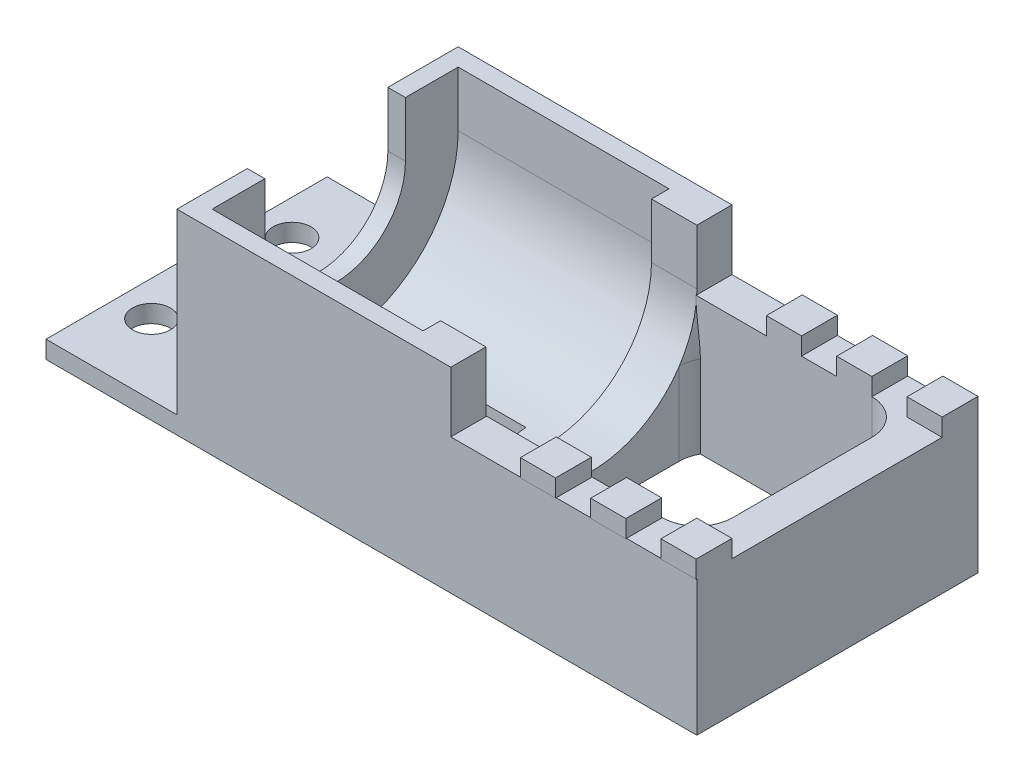
SolidWorks part; units mm, degrees
ref_plane "Front Plane" through (0, 0, 0) normal (0, 0, 1) x (1, 0, 0)
ref_plane "Top Plane" through (0, 0, 0) normal (0, 1, 0) x (1, 0, 0)
ref_plane "Right Plane" through (0, 0, 0) normal (1, 0, 0) x (0, 0, -1)
sketch "Sketch1" plane through (0, 0, 0) normal (0, 0, 1) x (1, 0, 0)
  line L1 (-76.2, -50.8) -> (76.2, -50.8)
  line L2 (-76.2, -50.8) -> (-76.2, 0)
  line L3 (-76.2, 0) -> (76.2, 0)
  line L4 (76.2, -50.8) -> (76.2, 0)
  line L5 (-76.2, -50.8) -> (76.2, 0) construction
  line L6 (-76.2, 0) -> (76.2, -50.8) construction
  point P0 (0, 0)
  dimension "D1" = 152.4
  dimension "D2" = 50.8
  dimension "D3" = 76.2
extrude "Boss-Extrude1" add sketch "Sketch1" along normal mid plane 50.8
sketch "Sketch2" plane through (0, 0, 0) normal (0, 0, 1) x (1, 0, 0)
  line L0 (-152.4829, -25.4) -> (19.6294, -25.4) construction
  line L1 (-49.3609, -3.175) -> (-49.3609, -12.7)
  line L2 (76.2, 0) -> (-76.2, 0) construction
  line L3 (76.2, 0) -> (-76.2, 0) construction
  line L4 (-11.2609, -3.175) -> (-11.2609, -6.35)
  line L5 (-11.2609, -25.4) -> (-11.2609, -3.175) construction
  line L6 (-128.4172, -25.4) -> (-157.8092, -25.4)
  line L7 (19.6294, -25.4) -> (20.7431, -25.4)
  line L8 (-607.3619, -25.4) -> (19.6294, -25.4) construction
  line L9 (-49.3609, -3.175) -> (-11.2609, -3.175)
  line L10 (19.6294, -25.4) -> (-128.4172, -25.4)
  line L11 (-11.2609, -6.35) -> (-4.6569, -6.35)
  line L12 (-4.6569, -6.35) -> (-4.6569, -15.494)
  line L13 (-4.6569, -15.494) -> (20.7431, -15.494)
  line L14 (-49.3609, -12.7) -> (-220.2024, -12.7)
  line L15 (-220.2024, -12.7) -> (-220.2024, -25.4)
  line L16 (-220.2024, -25.4) -> (-157.8092, -25.4)
  line L20 (20.7431, -15.494) -> (20.7431, -25.4)
  line L21 (-76.2, 0) -> (-76.2, -50.8) construction
  point P23 (-11.2609, -25.4)
  dimension "D1" = 22.225
  dimension "D2" = 38.1
  dimension "D3" = 25.4
  dimension "D4" = 32.004
  dimension "D5" = 9.906
  dimension "D6" = 3.175
  dimension "D7" = 26.8391
  dimension "D8" = 25.4
  dimension "D9" = 12.7
revolve "Cut-Revolve1" cut sketch "Sketch2" angle 360 about L0
sketch "Sketch38" plane through (20.7431, 0, 0) normal (1, 0, 0) x (0, 0, -1)
  line L1 (-10, -35.4) -> (10, -35.4)
  line L2 (-10, -35.4) -> (-10, -15.4)
  line L3 (-10, -15.4) -> (10, -15.4)
  line L4 (10, -35.4) -> (10, -15.4)
  line L5 (-10, -35.4) -> (10, -15.4) construction
  line L6 (-10, -15.4) -> (10, -35.4) construction
  circle A0 centre (0, -25.4) radius 9.906 construction
  point P1 (0, -25.4)
  dimension "D1" = 20
  dimension "D2" = 20
extrude "Cut-Extrude33" cut sketch "Sketch38" against normal offset from surface (23.8125 mm away) 1.5875 up to face at (-4.6569, -25.4, 19.05)
sketch "Sketch37" plane through (76.2, 0, 0) normal (1, 0, 0) x (0, 0, -1)
  line L0 (25.4, -50.8) -> (25.4, 0) construction
  line L1 (-25.4, 0) -> (25.4, 0)
  line L2 (-25.4, 0) -> (-25.4, -25.4)
  line L3 (-25.4, -25.4) -> (25.4, -25.4)
  line L4 (25.4, 0) -> (25.4, -25.4)
  line L5 (10, -35.4) -> (10, -15.4) construction
  point P7 (0, -25.4)
  point P11 (0, 0)
  point P14 (10, -25.4)
extrude "Cut-Extrude32" cut sketch "Sketch37" against normal through all
sketch "Sketch39" plane through (0, -25.4, 0) normal (0, 1, 0) x (1, 0, 0)
  line L24 (-49.3609, -12.7) -> (-76.2, -12.7)
  line L25 (-76.2, -12.7) -> (-76.2, -25.4)
  line L26 (-76.2, -25.4) -> (76.2, -25.4)
  line L27 (76.2, -25.4) -> (76.2, 25.4)
  line L28 (76.2, 25.4) -> (-76.2, 25.4)
  line L29 (-76.2, 25.4) -> (-76.2, 12.7)
  line L30 (-76.2, 12.7) -> (-49.3609, 12.7)
  line L31 (-49.3609, 12.7) -> (-49.3609, 22.225)
  line L32 (-49.3609, 22.225) -> (-11.2609, 22.225)
  line L33 (-11.2609, 22.225) -> (-11.2609, 19.05)
  line L34 (-11.2609, 19.05) -> (-4.6569, 19.05)
  line L35 (-4.6569, 19.05) -> (-4.6569, 9.906)
  line L36 (-4.6569, 9.906) -> (-3.0694, 9.906)
  line L37 (-3.0694, 9.906) -> (-3.0694, 10)
  line L38 (-3.0694, 9.906) -> (-3.0694, 10)
  line L39 (20.7431, 10) -> (20.7431, -10)
  line L40 (-3.0694, 10) -> (20.7431, 10)
  line L41 (-3.0694, 10) -> (20.7431, 10)
  line L42 (-3.0694, -9.906) -> (-4.6569, -9.906)
  line L43 (-4.6569, -9.906) -> (-4.6569, -19.05)
  line L44 (-4.6569, -19.05) -> (-11.2609, -19.05)
  line L45 (-11.2609, -19.05) -> (-11.2609, -22.225)
  line L46 (-11.2609, -22.225) -> (-49.3609, -22.225)
  line L47 (-49.3609, -22.225) -> (-49.3609, -12.7)
  line L48 (-49.3609, -12.7) -> (-76.2, -12.7)
  line L49 (-76.2, -12.7) -> (-76.2, -25.4)
  line L50 (-76.2, -25.4) -> (76.2, -25.4)
  line L51 (76.2, -25.4) -> (76.2, 25.4)
  line L52 (76.2, 25.4) -> (-76.2, 25.4)
  line L53 (-76.2, 25.4) -> (-76.2, 12.7)
  line L54 (-76.2, 12.7) -> (-49.3609, 12.7)
  line L55 (-49.3609, 12.7) -> (-49.3609, 22.225)
  line L56 (-49.3609, 22.225) -> (-11.2609, 22.225)
  line L57 (-11.2609, 22.225) -> (-11.2609, 19.05)
  line L58 (-11.2609, 19.05) -> (-4.6569, 19.05)
  line L59 (-4.6569, 19.05) -> (-4.6569, 9.906)
  line L60 (-4.6569, 9.906) -> (-3.0694, 9.906)
  line L61 (20.7431, -10) -> (-3.0694, -10)
  line L62 (20.7431, -10) -> (-3.0694, -10)
  line L63 (20.7431, 10) -> (20.7431, -10)
  line L64 (-3.0694, -10) -> (-3.0694, -9.906)
  line L65 (-3.0694, -10) -> (-3.0694, -9.906)
  line L66 (-3.0694, -9.906) -> (-4.6569, -9.906)
  line L67 (-4.6569, -9.906) -> (-4.6569, -19.05)
  line L68 (-4.6569, -19.05) -> (-11.2609, -19.05)
  line L69 (-11.2609, -19.05) -> (-11.2609, -22.225)
  line L70 (-11.2609, -22.225) -> (-49.3609, -22.225)
  line L71 (-49.3609, -22.225) -> (-49.3609, -12.7)
  dimension "D1" = 0
extrude "Boss-Extrude5" add sketch "Sketch39" along normal blind 25.4
ref_axis "Axis1" through (-3.0694, -25.4, 0) along (-1, 0, 0)
ref_plane "Plane_Mid" through (0, -25.4, 0) normal (0, 1, 0) x (1, 0, 0)
sketch "Sketch45" plane through (0, 0, 0) normal (0, 0, 1) x (1, 0, 0)
  line L2 (76.2, 0) -> (-3.0694, 0)
  line L4 (76.2, 0) -> (76.2, -19.05)
  line L5 (76.2, -19.05) -> (-3.0694, -19.05)
  line L6 (-3.0694, -25.4) -> (-4.6569, -25.4) construction
  line L8 (-3.0694, 0) -> (-3.0694, -19.05)
  dimension "D2" = 6.35
extrude "Cut-Extrude54" cut sketch "Sketch45" against normal through all both and the other way through all
sketch "Sketch53" plane through (20.7431, 0, 0) normal (-1, 0, 0) x (0, 0, 1)
  circle A0 centre (0, -25.4) radius 2
  dimension "D1" = 4
extrude "Cut-Extrude46" cut sketch "Sketch53" against normal blind 0.0254
sketch "Sketch72" plane through (0, -19.05, 0) normal (0, 1, 0) x (1, 0, 0)
  line L0 (-3.0694, -25.4) -> (-3.0694, -13.175)
  line L1 (-3.0694, -10) -> (-3.0694, -25.4) construction
  line L2 (-3.0694, -13.175) -> (23.9181, -13.175)
  line L3 (23.9181, -13.175) -> (23.9181, 13.175)
  line L4 (23.9181, 13.175) -> (-3.0694, 13.175)
  line L5 (-3.0694, 25.4) -> (-3.0694, 10) construction
  line L6 (-3.0694, 13.175) -> (-3.0694, 25.4)
  line L7 (-3.0694, 25.4) -> (76.2, 25.4)
  line L8 (76.2, 25.4) -> (76.2, -25.4)
  line L9 (76.2, -25.4) -> (-3.0694, -25.4)
  line L10 (-3.0694, -10) -> (20.7431, -10) construction
  line L11 (-3.0694, -10) -> (-3.0694, -13.175) construction
  line L12 (20.7431, -10) -> (23.9181, -10) construction
  line L13 (20.7431, 10) -> (20.7431, 13.175) construction
  dimension "D1" = 3.175
sketch "Sketch61" plane through (-4.6569, 0, 0) normal (-1, 0, 0) x (0, 0, 1)
  circle A0 centre (0, -25.4) radius 9.525
  circle A1 centre (0, -25.4) radius 9.906
  arc A2 (-9.906, -25.4) -> (9.906, -25.4) centre (0, -25.4) ccw construction
  dimension "D1" = 19.05
extrude "Boss-Extrude11" add sketch "Sketch61" against normal up to surface (1.5875 mm away) up to face at (-3.0694, -17.3088, 0)
sketch "Sketch70" plane through (0, 0, 0) normal (0, 1, 0) x (1, 0, 0)
  line L1 (-4.6569, 9.906) -> (-3.0694, 9.906)
  line L2 (-4.6569, 9.906) -> (-4.6569, -9.906)
  line L3 (-4.6569, -9.906) -> (-3.0694, -9.906)
  line L4 (-3.0694, 9.906) -> (-3.0694, -9.906)
extrude "Boss-Extrude17" add sketch "Sketch70" against normal up to next
sketch "Sketch76" plane through (0, -35.4, 0) normal (0, 1, 0) x (1, 0, 0)
  line L5 (-3.0694, -10) -> (20.7431, -10)
  line L6 (20.7431, -10) -> (20.7431, 10)
  line L9 (20.7431, 10) -> (-3.0694, 10)
  line L10 (-3.0694, 10) -> (-3.0694, -10)
  line L11 (-3.0694, -10) -> (20.7431, -10)
  line L12 (20.7431, -10) -> (20.7431, 10)
  line L13 (20.7431, 10) -> (-3.0694, 10)
  line L14 (-3.0694, 10) -> (-3.0694, -10)
  dimension "D1" = 0
extrude "Cut-Extrude58" cut sketch "Sketch76" against normal through all
sketch "Sketch86" plane through (0, -19.05, 0) normal (0, 1, 0) x (1, 0, 0)
  line L8 (-3.0694, -25.4) -> (76.2, -25.4)
  line L9 (-3.0694, -25.4) -> (76.2, -25.4)
  line L10 (76.2, -25.4) -> (76.2, 25.4)
  line L11 (76.2, -25.4) -> (76.2, 25.4)
  line L12 (76.2, 25.4) -> (-3.0694, 25.4)
  line L13 (76.2, 25.4) -> (-3.0694, 25.4)
  line L16 (20.7431, 10) -> (20.7431, -10)
  line L25 (20.7431, -10) -> (-3.0694, -10)
  line L26 (-3.0694, -10) -> (-3.0694, -25.4)
  line L30 (-3.0694, 25.4) -> (-3.0694, 10)
  line L31 (-3.0694, 10) -> (20.7431, 10)
  line L32 (20.7431, 10) -> (20.7431, -10)
  line L41 (20.7431, -10) -> (-3.0694, -10)
  line L42 (-3.0694, -10) -> (-3.0694, -25.4)
  line L46 (-3.0694, 25.4) -> (-3.0694, 10)
  line L47 (-3.0694, 10) -> (20.7431, 10)
  dimension "D1" = 0
extrude "Boss-Extrude24" add sketch "Sketch86" along normal blind 3.175
ref_plane "Plane1" through (-74.7609, 0, 0) normal (1, 0, 0) x (0, 0, -1)
sketch "Sketch89" plane through (0, 0, 0) normal (0, 1, 0) x (1, 0, 0)
  line L0 (-3.0694, 0) -> (-4.6569, 0) construction
  line L1 (-38.3605, -3.81) -> (-18.7213, -3.81)
  line L2 (-38.3605, -3.81) -> (-38.3605, 3.81)
  line L3 (-38.3605, 3.81) -> (-18.7213, 3.81)
  line L4 (-18.7213, -3.81) -> (-18.7213, 3.81)
  line L5 (-38.3605, -3.81) -> (-18.7213, 3.81) construction
  line L6 (-38.3605, 3.81) -> (-18.7213, -3.81) construction
  point P4 (-28.5409, 0)
extrude "Cut-Extrude64" cut sketch "Sketch89" against normal through all both and the other way through all
sketch "Sketch77" plane through (0, 0, 0) normal (0, 0, 1) x (1, 0, 0)
  line L0 (20.7431, -24.0284) -> (23.9181, -24.0284)
  line L1 (-3.0694, -26.7716) -> (20.7431, -26.7716)
  line L2 (-3.0694, -26.7716) -> (-3.0694, -24.0284)
  line L3 (-3.0694, -24.0284) -> (20.7431, -24.0284)
  line L4 (20.7431, -26.7716) -> (20.7431, -24.0284) construction
  line L5 (-3.0694, -26.7716) -> (20.7431, -24.0284) construction
  line L6 (-3.0694, -24.0284) -> (20.7431, -26.7716) construction
  line L7 (23.9181, -24.0284) -> (23.9181, -26.7716)
  line L8 (23.9181, -26.7716) -> (20.7431, -26.7716)
  line L9 (-3.0694, -25.4) -> (-4.6569, -25.4) construction
  line L10 (-3.0694, -15.875) -> (-3.0694, -50.8) construction
  line L11 (20.7431, -15.875) -> (20.7431, -50.8) construction
  point P0 (8.8368, -25.4)
  dimension "D1" = 3.175
  dimension "D2" = 2.7432
extrude "Cut-Extrude59" cut sketch "Sketch77" against normal through all both and the other way through all
sketch "Sketch96" plane through (0, 0, 25.4) normal (0, 0, 1) x (1, 0, 0)
  line L0 (-39.6347, 0) -> (-39.6347, -50.8) construction
  line L1 (-76.2, 0) -> (-3.0694, 0) construction
  line L2 (-76.2, -50.8) -> (76.2, -50.8) construction
  line L3 (-55.5097, -15.4427) -> (-23.7597, -15.4427)
  arc A0 (-23.7597, -15.4427) -> (-55.5097, -15.4427) centre (-39.6347, -32.1115) ccw
  point P8 (-39.6347, -15.4427)
  point P10 (-39.6347, -9.0927)
  dimension "D2" = 6.35
  dimension "D1" = 31.75
extrude "Cut-Extrude71" cut sketch "Sketch96" against normal through all
sketch "Sketch97" plane through (0, 0, 0) normal (0, 1, 0) x (1, 0, 0)
  line L0 (-76.2, -25.4) -> (-3.0694, -25.4) construction
  line L1 (-76.2, 25.4) -> (-52.5359, 25.4)
  line L2 (-76.2, 25.4) -> (-76.2, -25.4)
  line L3 (-76.2, -25.4) -> (-52.5359, -25.4)
  line L4 (-52.5359, 25.4) -> (-52.5359, -25.4)
  line L5 (-49.3609, 12.7) -> (-49.3609, 22.225) construction
  dimension "D1" = 3.175
extrude "Cut-Extrude72" cut sketch "Sketch97" against normal offset from surface (47.625 mm away) 3.175 up to face at (-28.5409, -50.8, 0)
sketch "Sketch98" plane through (0, -47.625, 0) normal (0, 1, 0) x (1, 0, 0)
  line L0 (-76.2, -25.4) -> (-76.2, 25.4) construction
  circle A0 centre (-69.85, 12.7) radius 3.429
  circle A1 centre (-57.15, 12.7) radius 3.429
  circle A2 centre (-57.15, 0) radius 3.429
  circle A3 centre (-57.15, -12.7) radius 3.429
  circle A4 centre (-69.85, 0) radius 3.429
  circle A5 centre (-69.85, -12.7) radius 3.429
  dimension "D1" = 6.858
  dimension "D2" = 76.2
  dimension "D3" = 6.35
  dimension "D4" = 12.7
  dimension "D5" = 2
  dimension "D6" = 3
extrude "Cut-Extrude73" cut sketch "Sketch98" against normal through all
ref_plane "Plane2" through (0, -25.4, 0) normal (0, 1, 0) x (1, 0, 0)
sketch "Sketch99" plane through (0, -25.4, 0) normal (0, 1, 0) x (1, 0, 0)
  line L1 (-3.0694, -25.4) -> (76.2, -25.4)
  line L2 (-3.0694, -25.4) -> (-3.0694, 25.4)
  line L3 (-3.0694, 25.4) -> (76.2, 25.4)
  line L4 (76.2, -25.4) -> (76.2, 25.4)
extrude "Cut-Extrude74" cut sketch "Sketch99" along normal through all
sketch "Sketch100" plane through (0, -25.4, 0) normal (0, 1, 0) x (1, 0, 0)
  line L0 (-3.0694, -25.4) -> (23.9181, -25.4) construction
  line L1 (-3.0694, -25.4) -> (76.2, -25.4)
  line L2 (-3.0694, -25.4) -> (-3.0694, 25.4)
  line L3 (-3.0694, 25.4) -> (76.2, 25.4)
  line L4 (76.2, -25.4) -> (76.2, 25.4)
  line L5 (-3.0694, 25.4) -> (76.2, 25.4) construction
  line L6 (-3.0694, -10) -> (-3.0694, -25.4) construction
extrude "Cut-Extrude75" cut sketch "Sketch100" against normal blind 2.2225
sketch "Sketch101" plane through (0, -25.4, 0) normal (0, 1, 0) x (1, 0, 0)
  line L0 (-3.0694, 25.4) -> (76.2, 25.4) construction
  line L1 (47.7306, 25.4) -> (52.3026, 25.4)
  line L2 (47.7306, 25.4) -> (47.7306, -25.4)
  line L3 (47.7306, -25.4) -> (52.3026, -25.4)
  line L4 (52.3026, 25.4) -> (52.3026, -25.4)
  line L6 (-3.0694, -25.4) -> (-3.0694, -13.175) construction
  dimension "D1" = 4.572
  dimension "D2" = 50.8
extrude "Cut-Extrude76" cut sketch "Sketch101" against normal blind 6.0579
sketch "Sketch103" plane through (0, -27.6225, 0) normal (0, 1, 0) x (1, 0, 0)
  line L0 (-3.0694, -25.4) -> (-3.0694, -13.175) construction
  line L1 (-3.0694, 0) -> (-4.6569, 0) construction
  line L2 (41.3806, 22.225) -> (-3.0694, 22.225)
  line L3 (41.3806, 22.225) -> (41.3806, -22.225)
  line L4 (41.3806, -22.225) -> (-3.0694, -22.225)
  line L5 (-3.0694, 22.225) -> (-3.0694, -22.225)
  line L6 (-3.0694, 25.4) -> (76.2, 25.4) construction
  line L7 (47.7306, -25.4) -> (47.7306, 25.4) construction
  point P6 (41.3806, 0)
  dimension "D1" = 3.175
  dimension "D2" = 6.35
extrude "Cut-Extrude78" cut sketch "Sketch103" against normal through all
sketch "Sketch104" plane through (-4.6569, 0, 0) normal (-1, 0, 0) x (0, 0, 1)
  line L3 (19.05, -25.4) -> (19.05, 0)
  line L4 (19.05, 0) -> (-19.05, 0)
  line L5 (-19.05, 0) -> (-19.05, -25.4)
  line L6 (19.05, -25.4) -> (19.05, 0)
  line L7 (19.05, 0) -> (-19.05, 0)
  line L8 (-19.05, 0) -> (-19.05, -25.4)
  arc A1 (-19.05, -25.4) -> (19.05, -25.4) centre (0, -25.4) ccw
  arc A2 (-19.05, -25.4) -> (19.05, -25.4) centre (0, -25.4) ccw
  dimension "D1" = 0
extrude "Cut-Extrude79" cut sketch "Sketch104" against normal up to next
sketch "Sketch105" plane through (0, -50.8, 0) normal (0, 1, 0) x (1, 0, 0)
  line L0 (41.3806, 22.225) -> (-3.0694, 22.225) construction
  line L1 (-3.0694, 22.225) -> (41.3806, 22.225)
  line L2 (-3.0694, 22.225) -> (-3.0694, 47.625)
  line L3 (-3.0694, 47.625) -> (41.3806, 47.625)
  line L4 (41.3806, 22.225) -> (41.3806, 47.625)
  line L5 (0, 0) -> (31.7243, 0) construction
  line L6 (-3.0694, 19.05) -> (-3.0694, 25.4) construction
  line L7 (41.3806, -22.225) -> (41.3806, 22.225) construction
  line L8 (41.3806, -22.225) -> (41.3806, -47.625)
  line L9 (-3.0694, -47.625) -> (41.3806, -47.625)
  line L10 (-3.0694, -22.225) -> (-3.0694, -47.625)
  line L11 (-3.0694, -22.225) -> (41.3806, -22.225)
  dimension "D1" = 25.4
extrude "Boss-Extrude25" add sketch "Sketch105" along normal up to surface (23.1775 mm away) up to face at (20.7431, -27.6225, 0)
sketch "Sketch106" plane through (0, -27.6225, 0) normal (0, 1, 0) x (1, 0, 0)
  line L0 (76.2, 25.4) -> (52.3026, 25.4) construction
  line L1 (76.2, 25.4) -> (58.6526, 25.4)
  line L2 (76.2, 25.4) -> (76.2, -25.4)
  line L3 (76.2, -25.4) -> (58.6526, -25.4)
  line L4 (58.6526, 25.4) -> (58.6526, -25.4)
  line L5 (76.2, -25.4) -> (76.2, 25.4) construction
  line L6 (52.3026, -25.4) -> (76.2, -25.4) construction
  line L7 (52.3026, -25.4) -> (52.3026, 25.4) construction
  dimension "D1" = 6.35
extrude "Cut-Extrude80" cut sketch "Sketch106" against normal through all
fillet "Fillet1" radius 6.35 14 edges at (-3.0694, -39.2112, -47.625) (41.3806, -39.2112, -47.625) (41.3806, -39.2112, -25.4) (58.6526, -39.2112, -25.4) (58.6526, -39.2112, 25.4) (41.3806, -39.2112, 25.4) (41.3806, -39.2112, 47.625) (-3.0694, -39.2112, 47.625) (-3.0694, -39.2112, 25.4) (-3.0694, -39.2112, 22.225) (-3.0694, -39.2112, -22.225) (41.3806, -39.2112, -22.225) (41.3806, -39.2112, 22.225) (-3.0694, -39.2112, -25.4)
sketch "Sketch107" plane through (0, -27.6225, 0) normal (0, 1, 0) x (1, 0, 0)
  line L0 (47.7306, -25.4) -> (47.7306, 25.4) construction
  line L1 (22.3306, 47.625) -> (47.7306, 47.625)
  line L2 (22.3306, 47.625) -> (22.3306, 6.35)
  line L3 (22.3306, 6.35) -> (47.7306, 6.35)
  line L4 (47.7306, 47.625) -> (47.7306, 6.35)
  line L5 (3.2806, 47.625) -> (35.0306, 47.625) construction
  line L6 (0, 0) -> (41.3806, 0) construction
  line L7 (41.3806, -15.875) -> (41.3806, 15.875) construction
  line L8 (47.7306, -47.625) -> (47.7306, -6.35)
  line L9 (22.3306, -6.35) -> (47.7306, -6.35)
  line L10 (22.3306, -47.625) -> (22.3306, -6.35)
  line L11 (22.3306, -47.625) -> (47.7306, -47.625)
  dimension "D1" = 25.4
  dimension "D2" = 6.35
extrude "Cut-Extrude81" cut sketch "Sketch107" against normal up to surface (3.8354 mm away) up to face at (50.0166, -31.4579, 0)
sketch "Sketch108" plane through (0, -15.4427, 0) normal (0, 1, 0) x (1, 0, 0)
  line L0 (-52.5359, -25.4) -> (-23.7597, -25.4) construction
  line L1 (-52.5359, -25.4) -> (14.8431, -25.4)
  line L2 (-52.5359, -25.4) -> (-52.5359, 39.7712)
  line L3 (-52.5359, 39.7712) -> (14.8431, 39.7712)
  line L4 (14.8431, -25.4) -> (14.8431, 39.7712)
extrude "Cut-Extrude82" cut sketch "Sketch108" along normal through all
sketch "Sketch109" plane through (0, -31.4579, 0) normal (0, 1, 0) x (1, 0, 0)
  line L16 (52.3026, 25.4) -> (47.7306, 25.4)
  line L17 (41.3806, 31.75) -> (41.3806, 41.275)
  line L18 (35.0306, 47.625) -> (22.3306, 47.625)
  line L19 (22.3306, 47.625) -> (22.3306, 22.225)
  line L20 (22.3306, 22.225) -> (35.0306, 22.225)
  line L21 (41.3806, 15.875) -> (41.3806, 6.35)
  line L22 (41.3806, 6.35) -> (47.7306, 6.35)
  line L23 (47.7306, 6.35) -> (47.7306, -6.35)
  line L24 (47.7306, -6.35) -> (41.3806, -6.35)
  line L25 (41.3806, -6.35) -> (41.3806, -15.875)
  line L26 (35.0306, -22.225) -> (22.3306, -22.225)
  line L27 (22.3306, -22.225) -> (22.3306, -47.625)
  line L28 (22.3306, -47.625) -> (35.0306, -47.625)
  line L29 (41.3806, -41.275) -> (41.3806, -31.75)
  line L30 (47.7306, -25.4) -> (52.3026, -25.4)
  line L31 (52.3026, -25.4) -> (52.3026, 25.4)
  line L32 (52.3026, 25.4) -> (47.7306, 25.4)
  line L33 (41.3806, 31.75) -> (41.3806, 41.275)
  line L34 (35.0306, 47.625) -> (22.3306, 47.625)
  line L35 (22.3306, 47.625) -> (22.3306, 22.225)
  line L36 (22.3306, 22.225) -> (35.0306, 22.225)
  line L37 (41.3806, 15.875) -> (41.3806, 6.35)
  line L38 (41.3806, 6.35) -> (47.7306, 6.35)
  line L39 (47.7306, 6.35) -> (47.7306, -6.35)
  line L40 (47.7306, -6.35) -> (41.3806, -6.35)
  line L41 (41.3806, -6.35) -> (41.3806, -15.875)
  line L42 (35.0306, -22.225) -> (22.3306, -22.225)
  line L43 (22.3306, -22.225) -> (22.3306, -47.625)
  line L44 (22.3306, -47.625) -> (35.0306, -47.625)
  line L45 (41.3806, -41.275) -> (41.3806, -31.75)
  line L46 (47.7306, -25.4) -> (52.3026, -25.4)
  line L47 (52.3026, -25.4) -> (52.3026, 25.4)
  arc A6 (41.3806, 31.75) -> (47.7306, 25.4) centre (47.7306, 31.75) ccw
  arc A7 (41.3806, 41.275) -> (35.0306, 47.625) centre (35.0306, 41.275) ccw
  arc A8 (41.3806, 15.875) -> (35.0306, 22.225) centre (35.0306, 15.875) ccw
  arc A9 (35.0306, -22.225) -> (41.3806, -15.875) centre (35.0306, -15.875) ccw
  arc A10 (35.0306, -47.625) -> (41.3806, -41.275) centre (35.0306, -41.275) ccw
  arc A11 (47.7306, -25.4) -> (41.3806, -31.75) centre (47.7306, -31.75) ccw
  arc A12 (41.3806, 31.75) -> (47.7306, 25.4) centre (47.7306, 31.75) ccw
  arc A13 (41.3806, 41.275) -> (35.0306, 47.625) centre (35.0306, 41.275) ccw
  arc A14 (41.3806, 15.875) -> (35.0306, 22.225) centre (35.0306, 15.875) ccw
  arc A15 (35.0306, -22.225) -> (41.3806, -15.875) centre (35.0306, -15.875) ccw
  arc A16 (35.0306, -47.625) -> (41.3806, -41.275) centre (35.0306, -41.275) ccw
  arc A17 (47.7306, -25.4) -> (41.3806, -31.75) centre (47.7306, -31.75) ccw
  dimension "D1" = 0
extrude "Boss-Extrude26" add sketch "Sketch109" along normal up to surface (3.8354 mm away) up to face at (56.1352, -27.6225, 0)
ref_point "Point1"
sketch "Sketch110" plane through (0, 0, 25.4) normal (0, 0, 1) x (1, 0, 0)
  line L1 (-76.2, -50.8) -> (82.1267, -50.8)
  line L2 (-76.2, -50.8) -> (-76.2, 4.0878)
  line L3 (-76.2, 4.0878) -> (82.1267, 4.0878)
  line L4 (82.1267, -50.8) -> (82.1267, 4.0878)
extrude "Cut-Extrude83" cut sketch "Sketch110" along normal through all
sketch "Sketch111" plane through (0, 0, -25.4) normal (0, 0, -1) x (-1, 0, 0)
  line L1 (76.2, -50.8) -> (-87.2258, -50.8)
  line L2 (76.2, -50.8) -> (76.2, 6.8745)
  line L3 (76.2, 6.8745) -> (-87.2258, 6.8745)
  line L4 (-87.2258, -50.8) -> (-87.2258, 6.8745)
extrude "Cut-Extrude84" cut sketch "Sketch111" along normal through all
sketch "Sketch112" plane through (0, -27.6225, 0) normal (0, 1, 0) x (1, 0, 0)
  line L1 (45.4111, -23.0804) -> (-3.0694, -23.0804)
  line L2 (45.4111, -23.0804) -> (45.4111, -18.9199)
  line L3 (45.4111, -18.9199) -> (-3.0694, -18.9199)
  line L4 (-3.0694, -23.0804) -> (-3.0694, -18.9199)
extrude "Boss-Extrude27" add sketch "Sketch112" against normal up to surface (23.1775 mm away) up to face at (-28.5409, -50.8, 0)
sketch "Sketch113" plane through (0, -27.6225, 0) normal (0, 1, 0) x (1, 0, 0)
  line L0 (-3.0694, 25.4) -> (-3.0694, 18.9199) construction
  line L1 (44.686, 23.4931) -> (-3.0694, 23.4931)
  line L2 (44.686, 23.4931) -> (44.686, 18.9199)
  line L3 (44.686, 18.9199) -> (-3.0694, 18.9199)
  line L4 (-3.0694, 23.4931) -> (-3.0694, 18.9199)
  spline S0 degree 3 poles (-3.0694, 18.9199) (-2.7943, 19.4222) (-2.4587, 19.8766) (-1.8671, 20.4883) (-1.6535, 20.6814) (-1.2078, 21.0329) (-0.9747, 21.1925) (-0.2456, 21.624) (0.2875, 21.8498) (1.105, 22.0734) (1.3817, 22.1298) (1.9436, 22.2056) (2.2301, 22.225) (2.5164, 22.225) knots 0 0 0 0 0.25 0.25 0.375 0.375 0.5 0.5 0.75 0.75 0.875 0.875 1 1 1 1 construction
extrude "Boss-Extrude28" add sketch "Sketch113" against normal up to surface (23.1775 mm away) up to face at (19.1556, -50.8, -1.1428)
sketch "Sketch117" plane through (0, -27.6225, 0) normal (0, 1, 0) x (1, 0, 0)
  line L0 (-3.0694, 25.4) -> (-3.0694, 19.05) construction
  line L1 (-3.0694, 49.9635) -> (72.0105, 49.9635)
  line L2 (-3.0694, 49.9635) -> (-3.0694, -40.6416)
  line L3 (-3.0694, -40.6416) -> (72.0105, -40.6416)
  line L4 (72.0105, 49.9635) -> (72.0105, -40.6416)
sketch "Sketch120" plane through (0, -27.6225, 0) normal (0, 1, 0) x (1, 0, 0)
  line L8 (-3.0694, 18.9199) -> (40.6029, 18.9199)
  line L9 (41.3806, 15.875) -> (41.3806, -15.875)
  line L10 (40.6029, -18.9199) -> (-3.0694, -18.9199)
  line L11 (-3.0694, -18.9199) -> (-3.0694, -25.4)
  line L12 (-3.0694, -25.4) -> (52.3026, -25.4)
  line L13 (58.6526, -19.05) -> (58.6526, 19.05)
  line L14 (52.3026, 25.4) -> (-3.0694, 25.4)
  line L15 (-3.0694, 25.4) -> (-3.0694, 18.9199)
  line L16 (-3.0694, 18.9199) -> (40.6029, 18.9199)
  line L17 (41.3806, 15.875) -> (41.3806, -15.875)
  line L18 (40.6029, -18.9199) -> (-3.0694, -18.9199)
  line L19 (-3.0694, -18.9199) -> (-3.0694, -25.4)
  line L20 (-3.0694, -25.4) -> (52.3026, -25.4)
  line L21 (58.6526, -19.05) -> (58.6526, 19.05)
  line L22 (52.3026, 25.4) -> (-3.0694, 25.4)
  line L23 (-3.0694, 25.4) -> (-3.0694, 18.9199)
  arc A4 (41.3806, 15.875) -> (40.6029, 18.9199) centre (35.0306, 15.875) ccw
  arc A5 (40.6029, -18.9199) -> (41.3806, -15.875) centre (35.0306, -15.875) ccw
  arc A6 (52.3026, -25.4) -> (58.6526, -19.05) centre (52.3026, -19.05) ccw
  arc A7 (58.6526, 19.05) -> (52.3026, 25.4) centre (52.3026, 19.05) ccw
  arc A8 (41.3806, 15.875) -> (40.6029, 18.9199) centre (35.0306, 15.875) ccw
  arc A9 (40.6029, -18.9199) -> (41.3806, -15.875) centre (35.0306, -15.875) ccw
  arc A10 (52.3026, -25.4) -> (58.6526, -19.05) centre (52.3026, -19.05) ccw
  arc A11 (58.6526, 19.05) -> (52.3026, 25.4) centre (52.3026, 19.05) ccw
  dimension "D1" = 0
extrude "Boss-Extrude31" add sketch "Sketch120" along normal blind 1.27
sketch "Sketch114" plane through (0, -26.3525, 0) normal (0, 1, 0) x (1, 0, 0)
  line L0 (-3.0694, 25.4) -> (52.3026, 25.4) construction
  line L1 (9.6306, 25.4) -> (15.9806, 25.4)
  line L2 (9.6306, 25.4) -> (9.6306, 18.9199)
  line L3 (9.6306, 18.9199) -> (15.9806, 18.9199)
  line L4 (15.9806, 25.4) -> (15.9806, 18.9199)
  line L5 (-3.0694, 18.9199) -> (40.6029, 18.9199) construction
  line L6 (-3.0694, 25.4) -> (-3.0694, 19.05) construction
  line L7 (22.3306, 25.4) -> (28.6806, 25.4)
  line L8 (22.3306, 25.4) -> (22.3306, 18.9199)
  line L9 (22.3306, 18.9199) -> (28.6806, 18.9199)
  line L10 (28.6806, 25.4) -> (28.6806, 18.9199)
  line L11 (35.0306, 25.4) -> (41.3806, 25.4)
  line L12 (35.0306, 25.4) -> (35.0306, 18.9199)
  line L13 (35.0306, 18.9199) -> (41.3806, 18.9199)
  line L14 (41.3806, 25.4) -> (41.3806, 18.9199)
  line L15 (22.3306, -19.05) -> (28.6806, -19.05)
  line L16 (22.3306, -19.05) -> (22.3306, -25.5301)
  line L17 (22.3306, -25.5301) -> (28.6806, -25.5301)
  line L18 (28.6806, -19.05) -> (28.6806, -25.5301)
  line L19 (35.0306, -19.05) -> (41.3806, -19.05)
  line L20 (35.0306, -19.05) -> (35.0306, -25.5301)
  line L21 (35.0306, -25.5301) -> (41.3806, -25.5301)
  line L22 (41.3806, -19.05) -> (41.3806, -25.5301)
  line L23 (9.6306, -19.05) -> (15.9806, -19.05)
  line L24 (9.6306, -19.05) -> (9.6306, -25.5301)
  line L25 (9.6306, -25.5301) -> (15.9806, -25.5301)
  line L26 (15.9806, -19.05) -> (15.9806, -25.5301)
  dimension "D1" = 6.35
  dimension "D2" = 12.7
  dimension "D3" = 3
  dimension "D4" = 2
extrude "Boss-Extrude29" add sketch "Sketch114" along normal blind 3.175
sketch "Sketch118" plane through (58.6526, 0, 0) normal (1, 0, 0) x (0, 0, -1)
  line L1 (-42.1291, -63.5171) -> (70.347, -63.5171)
  line L2 (-42.1291, -63.5171) -> (-42.1291, -3.6344)
  line L3 (-42.1291, -3.6344) -> (70.347, -3.6344)
  line L4 (70.347, -63.5171) -> (70.347, -3.6344)
extrude "Cut-Extrude86" cut sketch "Sketch118" against normal up to surface (17.272 mm away) up to face at (41.3806, -24.765, -22.16)
sketch "Sketch119" plane through (41.3806, 0, 0) normal (1, 0, 0) x (0, 0, -1)
  line L0 (25.4, -23.1775) -> (25.4, -50.8) construction
  line L1 (-25.4, -50.8) -> (25.4, -50.8)
  line L2 (-25.4, -50.8) -> (-25.4, -26.3525)
  line L3 (-25.4, -26.3525) -> (25.4, -26.3525)
  line L4 (25.4, -50.8) -> (25.4, -26.3525)
  line L6 (18.9199, -26.3525) -> (25.4, -26.3525) construction
extrude "Boss-Extrude30" add sketch "Sketch119" against normal blind 6.35
fillet "Fillet2" radius 6.35 2 edges at (35.0306, -38.5763, 18.9199) (35.0306, -38.5763, -18.9199)
